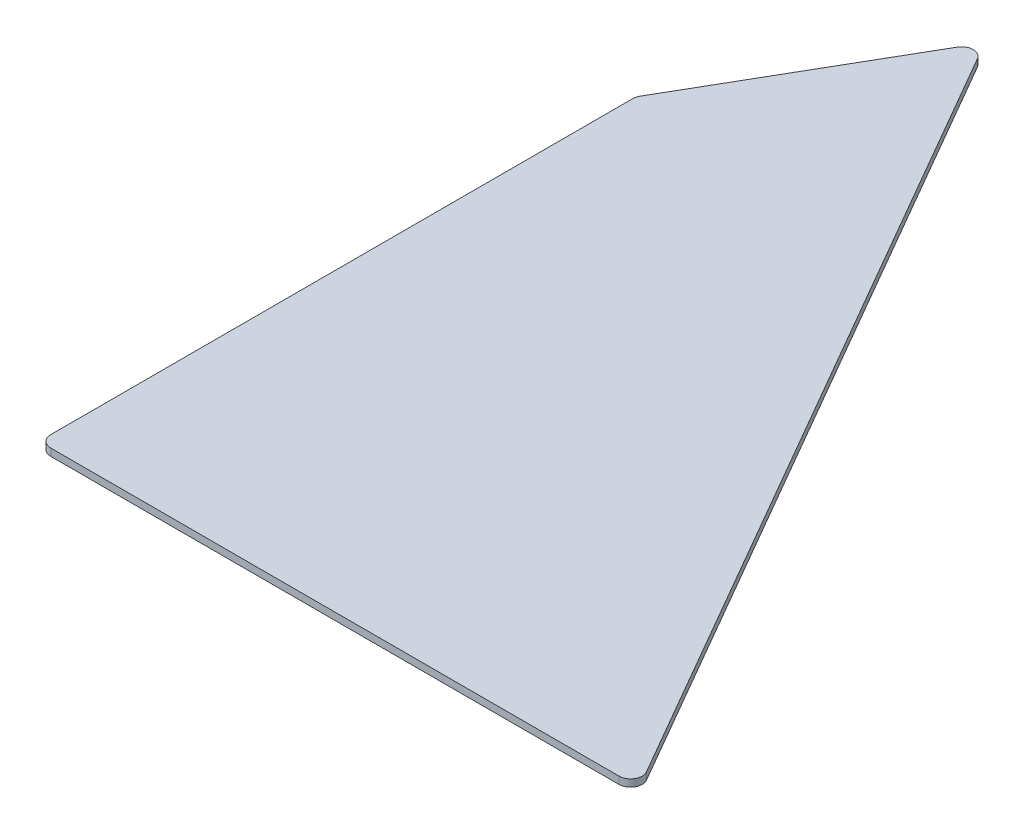
SolidWorks part; units mm, degrees
ref_plane "Front Plane" through (0, 0, 0) normal (0, 0, 1) x (1, 0, 0)
ref_plane "Top Plane" through (0, 0, 0) normal (0, 1, 0) x (1, 0, 0)
ref_plane "Right Plane" through (0, 0, 0) normal (1, 0, 0) x (0, 0, -1)
sketch "Sketch1" plane through (0, 0, 0) normal (0, 1, 0) x (1, 0, 0)
  line L0 (0, 0) -> (457.2, 0) construction
  line L1 (457.2, 0) -> (228.6, 395.9468) construction
  line L2 (228.6, 395.9468) -> (0, 0) construction
  line L3 (185.42, 25.4) -> (413.2059, 25.4)
  line L4 (413.2059, 25.4) -> (228.6, 345.1468)
  line L5 (228.6, 345.1468) -> (185.42, 270.3569)
  line L6 (185.42, 25.4) -> (185.42, 270.3569)
  line L7 (228.6, 345.1468) -> (43.9941, 25.4) construction
  line L8 (43.9941, 25.4) -> (413.2059, 25.4) construction
  line L9 (435.203, 12.7) -> (228.6, 370.5468)
  line L10 (228.6, 370.5468) -> (172.72, 273.7598)
  line L11 (172.72, 12.7) -> (172.72, 273.7598)
  line L12 (172.72, 12.7) -> (435.203, 12.7)
  dimension "D1" = 457.2
  dimension "D3" = 43.18
  dimension "D2" = 25.4
  dimension "D4" = 12.7
extrude "Boss-Extrude1" add sketch "Sketch1" along normal blind 6.35 contours L6 L3 L4 L5 | L11 L12 L9 L10 L3 L6 L5 L4 region at (266.1136, 0, -142.3365) region at (303.9615, 0, -17.1379)
extrude "Cut-Extrude2" cut sketch "Sketch1<3>" along normal blind 3.175 contours L11 L12 L9 L10 L3 L6 L5 L4 region at (303.9615, 0, -17.1379)
sketch "Sketch1<3>" plane through (0, 0, 0) normal (0, 1, 0) x (1, 0, 0) same geometry as "Sketch1"
fillet "Fillet1" radius 5.08 4 edges at (228.6, 4.7625, -370.5468) (172.72, 4.7625, -273.7598) (172.72, 4.7625, -12.7) (435.203, 4.7625, -12.7)
